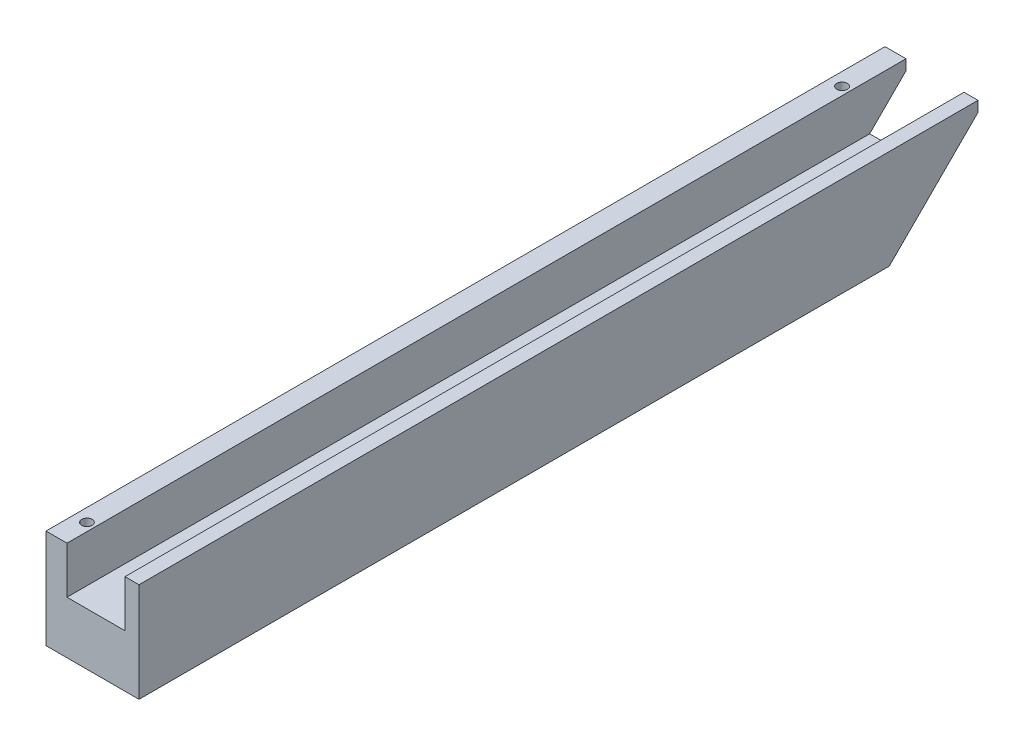
SolidWorks part; units mm, degrees
ref_plane "Front Plane" through (0, 0, 0) normal (0, 0, 1) x (1, 0, 0)
ref_plane "Top Plane" through (0, 0, 0) normal (0, 1, 0) x (1, 0, 0)
ref_plane "Right Plane" through (0, 0, 0) normal (1, 0, 0) x (0, 0, -1)
ref_axis "X-Axis" through (0, 0, 0) along (1, 0, 0)
ref_axis "Y-Axis" through (0, 42.2917, 0) along (0, -1, 0)
ref_axis "Z-Axis" through (0, 0, 55.0015) along (0, 0, -1)
sketch "Sketch1" plane through (0, 0, 0) normal (0, 0, 1) x (1, 0, 0)
  line L0 (3.9911, 6.7786) -> (6.9911, 6.7786)
  line L1 (6.9911, 6.7786) -> (6.9911, 0.0786)
  line L2 (6.9911, 0.0786) -> (15.2911, 0.0786)
  line L3 (15.2911, 0.0786) -> (15.2911, 6.7786)
  line L4 (15.2911, 6.7786) -> (17.2911, 6.7786)
  line L5 (17.2911, 6.7786) -> (17.2911, -7.4214)
  line L6 (17.2911, -7.4214) -> (3.9911, -7.4214)
  line L7 (3.9911, -7.4214) -> (3.9911, 6.7786)
  line L8 (-0.8459, -4.4214) -> (52.4677, -4.4214) construction
  line L9 (52.4677, -4.4214) -> (52.4677, 5.5786) construction
  line L10 (52.4677, 5.5786) -> (-1.8799, 5.5786) construction
  dimension "D1" = 3
  dimension "D2" = 2
  dimension "D3" = 8.3
  dimension "D4" = 7.5
  dimension "D5" = 14.2
  dimension "Largeur_Rail" = 13.3
  dimension "Profondeur_Rail" = 6.7
extrude "Rail-Extrude" add sketch "Sketch1" along normal blind 120
sketch "Sketch2" plane through (0, 6.7786, 0) normal (0, 1, 0) x (1, 0, 0)
  line L0 (5.8411, 0) -> (5.8411, -8) construction
  line L1 (6.9911, 0) -> (3.9911, 0) construction
  line L2 (3.9911, -120) -> (3.9911, 0) construction
  circle A0 centre (5.8411, -8) radius 0.75
  dimension "D1" = 1.5
  dimension "D2" = 8
  dimension "D3" = 1.85
extrude "First Hole" cut sketch "Sketch2" against normal through all
sketch "Sketch3" plane through (0, 6.7786, 0) normal (0, 1, 0) x (1, 0, 0)
  line L0 (5.8411, -8) -> (5.8411, -116) construction
  circle A0 centre (5.8411, -116) radius 0.75
  circle A1 centre (5.8411, -8) radius 0.75 construction
  dimension "D1" = 108
extrude "Last Hole" cut sketch "Sketch3" against normal through all
sketch "Sketch5" plane through (3.9911, 0, 0) normal (-1, 0, 0) x (0, 0, 1)
  line L5 (120, 6.7786) -> (0, 6.7786) construction
  line L6 (120, -7.4214) -> (0, -7.4214) construction
  line L7 (0, -5.4214) -> (10, -5.4214) construction
  line L8 (0, -5.4214) -> (0, -7.4214) construction
  line L9 (0, -7.4214) -> (10, -7.4214) construction
  line L10 (10, -5.4214) -> (10, -7.4214) construction
  line L11 (0, 6.7786) -> (0, -7.4214) construction
  line L12 (12.7, -7.4214) -> (0, 5.2786)
  line L13 (0, 5.2786) -> (0, -7.4214)
  line L14 (0, -7.4214) -> (12.7, -7.4214)
  dimension "D1" = 2
  dimension "D2" = 10
  dimension "D3" = 45
  dimension "D4" = 1.5
extrude "Angle" cut sketch "Sketch5" against normal through all
equation "\"Largeur Bande\"= 12.3"
equation "\"Largeur_Rail\"= \"Largeur Bande\" + 1"
equation "\"Profondeur Bande\"= 6.5"
equation "\"Profondeur_Rail\" = \"Profondeur Bande\" + 0.2"
equation "\"Largeur Feeder\"= \"Largeur Rail\" + 1.2 + 1.2 + 0.3"
equation "\"Largeur Rail\"= \"Largeur Bande\" + 1"
equation "\"D1@Boss-Extrude1\"=\"Largeur Feeder\"/2"
equation "\"D2@Boss-Extrude1\"=\"Largeur Feeder\"/2"
